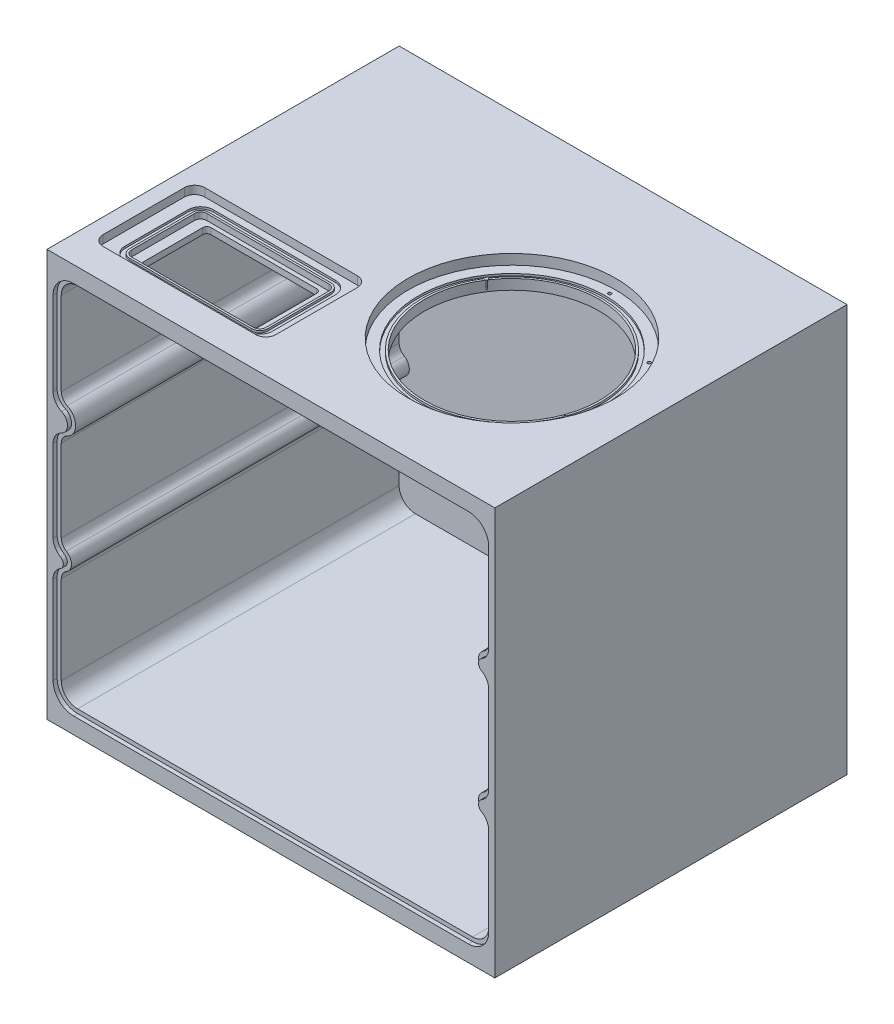
SolidWorks part; units mm, degrees
material "6061 Alloy"
ref_plane "Front Plane" through (0, 0, 0) normal (0, 0, 1) x (1, 0, 0)
ref_plane "Top Plane" through (0, 0, 0) normal (0, 1, 0) x (1, 0, 0)
ref_plane "Right Plane" through (0, 0, 0) normal (1, 0, 0) x (0, 0, -1)
sketch "Sketch1" plane through (0, 0, 0) normal (0, 0, 1) x (1, 0, 0)
  line L0 (0, 100) -> (0, -100) construction
  line L1 (-110, 100) -> (110, 100)
  line L2 (-110, 100) -> (-110, -100)
  line L3 (-110, -100) -> (110, -100)
  line L4 (110, 100) -> (110, -100)
  line L5 (-105, 22.9298) -> (-105, -25)
  line L6 (-105, -35) -> (-105, -90)
  line L7 (-105, 90) -> (105, 90)
  line L8 (-105, 90) -> (-105, 37.0702)
  line L9 (-105, -90) -> (105, -90)
  line L10 (105, 90) -> (105, 35)
  line L11 (105, 25) -> (105, -25)
  line L12 (105, -35) -> (105, -90)
  arc A1 (-105, 22.9298) -> (-105, 37.0702) centre (-105, 30) ccw
  arc A4 (-105, -35) -> (-105, -25) centre (-105, -30) ccw
  arc A6 (105, 35) -> (105, 25) centre (105, 30) ccw
  arc A7 (105, -25) -> (105, -35) centre (105, -30) ccw
  point P0 (0, 0)
  point P6 (0, 0)
  point P18 (0, 0)
  point P22 (0, 0)
  point P27 (-105.1131, 90)
  dimension "D9" = 60
  dimension "D10" = 60
  dimension "D1" = 220
  dimension "D2" = 200
  dimension "D3" = 210
  dimension "D4" = 180
  dimension "D5" = 90
  dimension "D6" = 105
  dimension "D8" = 100
  dimension "D12" = 5
  dimension "D13" = 60
  dimension "D14" = 60
extrude "Boss-Extrude1" add sketch "Sketch1" along normal blind 5 contours L2 L3 L4 L1
extrude "Boss-Extrude2" add sketch "Sketch1<3>" along normal blind 173
sketch "Sketch1<3>" plane through (0, 0, 0) normal (0, 0, 1) x (1, 0, 0) same geometry as "Sketch1"
fillet "Fillet1" radius 8 4 edges at (105, -90, 89) (-105, -90, 89) (105, 90, 89) (-105, 90, 89)
fillet "Fillet2" radius 5 8 edges at (105, -35, 89) (105, -25, 89) (105, 35, 89) (105, 25, 89) (-105, 37.0702, 89) (-105, 22.9298, 89) (-105, -25, 89) (-105, -35, 89)
sketch "Sketch2" plane through (0, 0, 173) normal (0, 0, 1) x (1, 0, 0)
  line L0 (107, -82) -> (107, -38.6603)
  line L1 (107, -21.3397) -> (107, 21.3397)
  line L2 (107, 38.6603) -> (107, 82)
  line L3 (97, 92) -> (-97, 92)
  line L4 (-107, 82) -> (-107, 40.9858)
  line L5 (-107, 19.0142) -> (-107, -21.3397)
  line L6 (-107, -38.6603) -> (-107, -82)
  line L7 (-97, -92) -> (97, -92)
  line L8 (105, -82) -> (105, -38.6603)
  line L9 (105, -21.3397) -> (105, 21.3397)
  line L10 (105, 38.6603) -> (105, 82)
  line L11 (97, 90) -> (-97, 90)
  line L12 (-105, 82) -> (-105, 40.9858)
  line L13 (-105, 19.0142) -> (-105, -21.3397)
  line L14 (-105, -38.6603) -> (-105, -82)
  line L15 (-97, -90) -> (97, -90)
  line L16 (105, -82) -> (105, -38.6603)
  line L17 (105, -21.3397) -> (105, 21.3397)
  line L18 (105, 38.6603) -> (105, 82)
  line L19 (97, 90) -> (-97, 90)
  line L20 (-105, 82) -> (-105, 40.9858)
  line L21 (-105, 19.0142) -> (-105, -21.3397)
  line L22 (-105, -38.6603) -> (-105, -82)
  line L23 (-97, -90) -> (97, -90)
  arc A0 (107, -38.6603) -> (103.5, -32.5981) centre (100, -38.6603) ccw
  arc A1 (103.5, -27.4019) -> (103.5, -32.5981) centre (105, -30) ccw
  arc A2 (103.5, -27.4019) -> (107, -21.3397) centre (100, -21.3397) ccw
  arc A3 (107, 21.3397) -> (103.5, 27.4019) centre (100, 21.3397) ccw
  arc A4 (103.5, 32.5981) -> (103.5, 27.4019) centre (105, 30) ccw
  arc A5 (103.5, 32.5981) -> (107, 38.6603) centre (100, 38.6603) ccw
  arc A6 (107, 82) -> (97, 92) centre (97, 82) ccw
  arc A7 (-97, 92) -> (-107, 82) centre (-97, 82) ccw
  arc A8 (-107, 40.9858) -> (-102.8997, 34.6147) centre (-100, 40.9858) ccw
  arc A9 (-102.8997, 25.3853) -> (-102.8997, 34.6147) centre (-105, 30) ccw
  arc A10 (-102.8997, 25.3853) -> (-107, 19.0142) centre (-100, 19.0142) ccw
  arc A11 (-107, -21.3397) -> (-103.5, -27.4019) centre (-100, -21.3397) ccw
  arc A12 (-103.5, -32.5981) -> (-103.5, -27.4019) centre (-105, -30) ccw
  arc A13 (-103.5, -32.5981) -> (-107, -38.6603) centre (-100, -38.6603) ccw
  arc A14 (-107, -82) -> (-97, -92) centre (-97, -82) ccw
  arc A15 (97, -92) -> (107, -82) centre (97, -82) ccw
  arc A16 (105, -38.6603) -> (102.5, -34.3301) centre (100, -38.6603) ccw
  arc A17 (102.5, -25.6699) -> (102.5, -34.3301) centre (105, -30) ccw
  arc A18 (102.5, -25.6699) -> (105, -21.3397) centre (100, -21.3397) ccw
  arc A19 (105, 21.3397) -> (102.5, 25.6699) centre (100, 21.3397) ccw
  arc A20 (102.5, 34.3301) -> (102.5, 25.6699) centre (105, 30) ccw
  arc A21 (102.5, 34.3301) -> (105, 38.6603) centre (100, 38.6603) ccw
  arc A22 (105, 82) -> (97, 90) centre (97, 82) ccw
  arc A23 (-97, 90) -> (-105, 82) centre (-97, 82) ccw
  arc A24 (-105, 40.9858) -> (-102.0712, 36.435) centre (-100, 40.9858) ccw
  arc A25 (-102.0712, 23.565) -> (-102.0712, 36.435) centre (-105, 30) ccw
  arc A26 (-102.0712, 23.565) -> (-105, 19.0142) centre (-100, 19.0142) ccw
  arc A27 (-105, -21.3397) -> (-102.5, -25.6699) centre (-100, -21.3397) ccw
  arc A28 (-102.5, -34.3301) -> (-102.5, -25.6699) centre (-105, -30) ccw
  arc A29 (-102.5, -34.3301) -> (-105, -38.6603) centre (-100, -38.6603) ccw
  arc A30 (-105, -82) -> (-97, -90) centre (-97, -82) ccw
  arc A31 (97, -90) -> (105, -82) centre (97, -82) ccw
  arc A32 (105, -38.6603) -> (102.5, -34.3301) centre (100, -38.6603) ccw
  arc A33 (102.5, -25.6699) -> (102.5, -34.3301) centre (105, -30) ccw
  arc A34 (102.5, -25.6699) -> (105, -21.3397) centre (100, -21.3397) ccw
  arc A35 (105, 21.3397) -> (102.5, 25.6699) centre (100, 21.3397) ccw
  arc A36 (102.5, 34.3301) -> (102.5, 25.6699) centre (105, 30) ccw
  arc A37 (102.5, 34.3301) -> (105, 38.6603) centre (100, 38.6603) ccw
  arc A38 (105, 82) -> (97, 90) centre (97, 82) ccw
  arc A39 (-97, 90) -> (-105, 82) centre (-97, 82) ccw
  arc A40 (-105, 40.9858) -> (-102.0712, 36.435) centre (-100, 40.9858) ccw
  arc A41 (-102.0712, 23.565) -> (-102.0712, 36.435) centre (-105, 30) ccw
  arc A42 (-102.0712, 23.565) -> (-105, 19.0142) centre (-100, 19.0142) ccw
  arc A43 (-105, -21.3397) -> (-102.5, -25.6699) centre (-100, -21.3397) ccw
  arc A44 (-102.5, -34.3301) -> (-102.5, -25.6699) centre (-105, -30) ccw
  arc A45 (-102.5, -34.3301) -> (-105, -38.6603) centre (-100, -38.6603) ccw
  arc A46 (-105, -82) -> (-97, -90) centre (-97, -82) ccw
  arc A47 (97, -90) -> (105, -82) centre (97, -82) ccw
  dimension "D1" = 0
  dimension "D2" = 2
sketch "Sketch4" plane through (0, 100, 0) normal (0, 1, 0) x (1, 0, 0)
  line L0 (110, -173) -> (110, 0) construction
  line L1 (110, -173) -> (-110, -173) construction
  circle A0 centre (42, -96.6) radius 43
  circle A1 centre (42, -96.6) radius 44
  circle A2 centre (42, -96.6) radius 46
  circle A3 centre (42, -96.6) radius 51
  dimension "D2" = 76.4
  dimension "D3" = 86
  dimension "D4" = 88
  dimension "D5" = 92
  dimension "D6" = 102
  dimension "D1" = 68
extrude "Cut-Extrude3" cut sketch "Sketch4" against normal blind 10 contours A0
extrude "Cut-Extrude4" cut sketch "Sketch4<3>" against normal blind 5 contours A3
sketch "Sketch4<3>" plane through (0, 100, 0) normal (0, 1, 0) x (1, 0, 0) same geometry as "Sketch4"
extrude "Cut-Extrude6" cut sketch "Sketch4<5>" against normal blind 6 contours A2 A1 region at (-2.6989, 100, 96.6)
sketch "Sketch4<5>" plane through (0, 100, 0) normal (0, 1, 0) x (1, 0, 0) same geometry as "Sketch4"
extrude "Cut-Extrude9" cut sketch "Sketch2" against normal blind 2
sketch "Sketch5" plane through (0, 95, 0) normal (0, 1, 0) x (1, 0, 0)
  line L0 (42, -96.6) -> (42, 9.4616) construction
  circle A0 centre (42, -48.6) radius 0.7835
  circle A1 centre (81.0692, -68.2699) radius 0.7835
  circle A2 centre (83.5692, -111.9397) radius 0.7835
  circle A3 centre (47, -135.9397) radius 0.7835
  circle A4 centre (7.9308, -116.2699) radius 0.7835
  circle A5 centre (5.4308, -72.6) radius 0.7835
  point P18 (44.5, -92.2699)
  dimension "D1" = 1.567
  dimension "D2" = 48
  dimension "D3" = 6
extrude "Cut-Extrude7" cut sketch "Sketch5" against normal blind 4
sketch "Sketch6" plane through (0, 100, 0) normal (0, 1, 0) x (1, 0, 0)
  line L0 (-110, -173) -> (-110, 0) construction
  line L1 (-88, -116.5) -> (-32, -116.5)
  line L2 (-88, -116.5) -> (-88, -149.5)
  line L3 (-88, -149.5) -> (-32, -149.5)
  line L4 (-32, -116.5) -> (-32, -149.5)
  line L5 (-88, -116.5) -> (-32, -149.5) construction
  line L6 (-88, -149.5) -> (-32, -116.5) construction
  line L7 (110, -173) -> (-110, -173) construction
  line L9 (-93, -114.5) -> (-27, -114.5)
  line L10 (-93, -114.5) -> (-93, -151.5)
  line L11 (-93, -151.5) -> (-27, -151.5)
  line L12 (-27, -114.5) -> (-27, -151.5)
  line L13 (-93, -114.5) -> (-27, -151.5) construction
  line L14 (-93, -151.5) -> (-27, -114.5) construction
  line L19 (-94, -113.5) -> (-26, -113.5)
  line L20 (-26, -113.5) -> (-26, -152.5)
  line L24 (-94, -152.5) -> (-26, -152.5)
  line L25 (-94, -113.5) -> (-94, -152.5)
  line L26 (-96.2, -111.3) -> (-23.8, -111.3)
  line L27 (-23.8, -111.3) -> (-23.8, -154.7)
  line L28 (-96.2, -154.7) -> (-23.8, -154.7)
  line L29 (-96.2, -111.3) -> (-96.2, -154.7)
  line L31 (-102.5, -108) -> (-17.5, -108)
  line L32 (-102.5, -108) -> (-102.5, -158)
  line L33 (-102.5, -158) -> (-17.5, -158)
  line L34 (-17.5, -108) -> (-17.5, -158)
  line L35 (-102.5, -108) -> (-17.5, -158) construction
  line L36 (-102.5, -158) -> (-17.5, -108) construction
  point P0 (-60, -133)
  point P9 (-60, -133)
  point P14 (-60, -133)
  point P23 (-60, -133)
  dimension "D1" = 50
  dimension "D2" = 40
  dimension "D3" = 56
  dimension "D4" = 33
  dimension "D5" = 66
  dimension "D6" = 37
  dimension "D7" = 1
  dimension "D8" = 2.2
  dimension "D9" = 85
  dimension "D10" = 50
extrude "Cut-Extrude8" cut sketch "Sketch6" against normal blind 10 contours L4 L1 L2 L3 region at (-60, 100, 133)
extrude "Cut-Extrude10" cut sketch "Sketch6<3>" against normal blind 4 contours L32 L33 L34 L31
sketch "Sketch6<3>" plane through (0, 100, 0) normal (0, 1, 0) x (1, 0, 0) same geometry as "Sketch6"
extrude "Cut-Extrude11" cut sketch "Sketch6<4>" against normal blind 7 contours L12 L9 L10 L11 L1 L4 L3 L2 region at (-60, 100, 115.2566)
sketch "Sketch6<4>" plane through (0, 100, 0) normal (0, 1, 0) x (1, 0, 0) same geometry as "Sketch6"
extrude "Cut-Extrude12" cut sketch "Sketch6<5>" against normal blind 5 contours L26 L29 L28 L27 L25 L19 L20 L24 region at (-60, 100, 112.1441)
sketch "Sketch6<5>" plane through (0, 100, 0) normal (0, 1, 0) x (1, 0, 0) same geometry as "Sketch6"
fillet "Fillet3" radius 2 4 edges at (-32, 91.5, 149.5) (-88, 91.5, 149.5) (-32, 91.5, 116.5) (-88, 91.5, 116.5)
fillet "Fillet4" radius 3 4 edges at (-27, 94.5, 151.5) (-93, 94.5, 151.5) (-27, 94.5, 114.5) (-93, 94.5, 114.5)
fillet "Fillet5" radius 4 4 edges at (-26, 95.5, 152.5) (-26, 95.5, 113.5) (-94, 95.5, 152.5) (-94, 95.5, 113.5)
fillet "Fillet6" radius 6.2 4 edges at (-23.8, 95.5, 154.7) (-96.2, 95.5, 154.7) (-23.8, 95.5, 111.3) (-96.2, 95.5, 111.3)
fillet "Fillet7" radius 5 4 edges at (-17.5, 98, 158) (-102.5, 98, 158) (-17.5, 98, 108) (-102.5, 98, 108)
